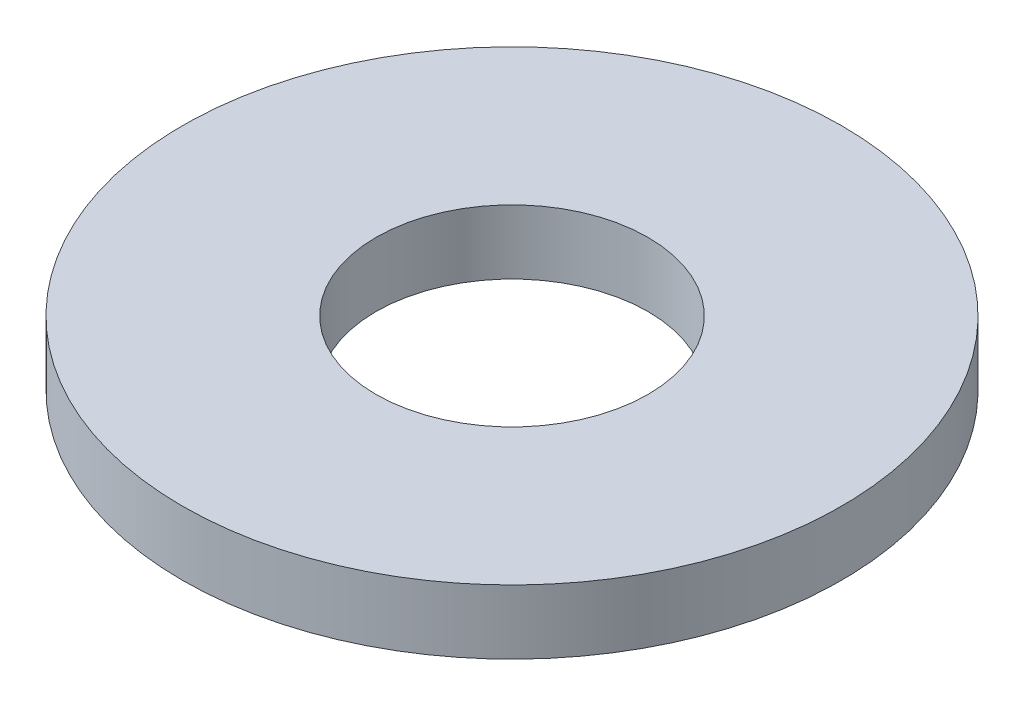
SolidWorks part; units mm, degrees
material "Alloy Steel"
ref_plane "Front Plane" through (0, 0, 0) normal (0, 0, 1) x (1, 0, 0)
ref_plane "Top Plane" through (0, 0, 0) normal (0, 1, 0) x (1, 0, 0)
ref_plane "Right Plane" through (0, 0, 0) normal (1, 0, 0) x (0, 0, -1)
sketch "Sketch1" plane through (0, 0, 0) normal (0, 1, 0) x (1, 0, 0)
  circle A0 centre (0, 0) radius 3.302
  circle A1 centre (0, 0) radius 8
  dimension "D1" = 16
  dimension "D2" = 6.604
extrude "Boss-Extrude1" add sketch "Sketch1" along normal blind 1.56
